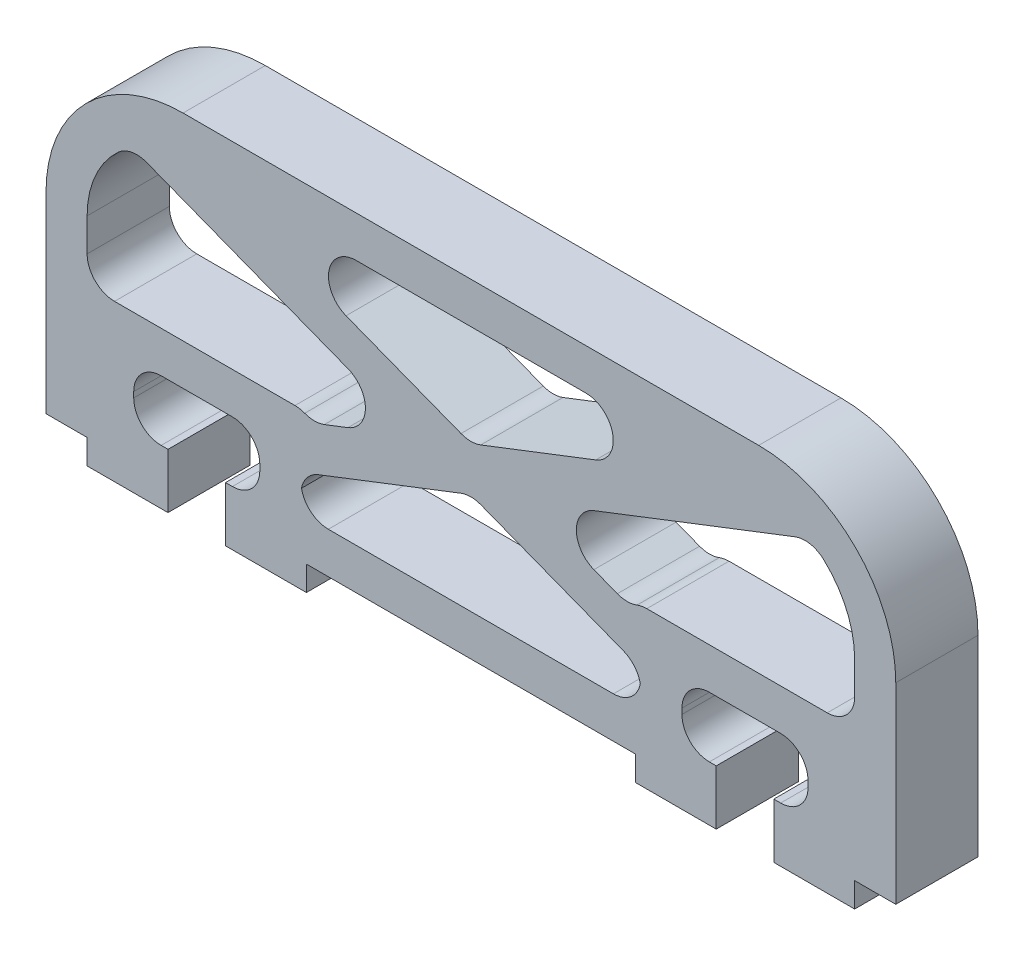
SolidWorks part; units mm, degrees
ref_plane "Front Plane" through (0, 0, 0) normal (0, 0, 1) x (1, 0, 0)
ref_plane "Top Plane" through (0, 0, 0) normal (0, 1, 0) x (1, 0, 0)
ref_plane "Right Plane" through (0, 0, 0) normal (1, 0, 0) x (0, 0, -1)
sketch "Sketch1" plane through (0, 0, 0) normal (0, 0, 1) x (1, 0, 0)
  line L0 (-10, -6.9) -> (-10, 6) construction
  line L1 (-15.5, 6) -> (15.5, 6)
  line L2 (-15.5, 6) -> (-15.5, -6)
  line L3 (-15.5, -6) -> (15.5, -6)
  line L4 (15.5, 6) -> (15.5, -6)
  line L5 (-15.5, 6) -> (15.5, -6) construction
  line L6 (-15.5, -6) -> (15.5, 6) construction
  line L7 (-15.5, -6) -> (-6, -6)
  line L9 (-14, -6.9) -> (-6, -6.9)
  line L10 (-6, -6) -> (-6, -6.9)
  line L11 (0, 6) -> (0, -6) construction
  line L12 (-11.05, -4.9) -> (-8.95, -4.9)
  line L13 (-11.05, -4.9) -> (-11.05, -6.9)
  line L14 (-11.05, -6.9) -> (-8.95, -6.9)
  line L15 (-8.95, -4.9) -> (-8.95, -6.9)
  line L16 (-11.05, -4.9) -> (-8.95, -6.9) construction
  line L17 (-11.05, -6.9) -> (-8.95, -4.9) construction
  line L18 (-12.3, -2.7) -> (-7.7, -2.7)
  line L19 (-12.3, -2.7) -> (-12.3, -4.9)
  line L20 (-12.3, -4.9) -> (-7.7, -4.9)
  line L21 (-7.7, -2.7) -> (-7.7, -4.9)
  line L22 (-12.3, -2.7) -> (-7.7, -4.9) construction
  line L23 (-12.3, -4.9) -> (-7.7, -2.7) construction
  line L24 (12.3, -2.7) -> (7.7, -2.7)
  line L25 (12.3, -2.7) -> (12.3, -4.9)
  line L26 (12.3, -4.9) -> (7.7, -4.9)
  line L27 (7.7, -2.7) -> (7.7, -4.9)
  line L28 (11.05, -4.9) -> (8.95, -4.9)
  line L29 (11.05, -4.9) -> (11.05, -6.9)
  line L30 (11.05, -6.9) -> (8.95, -6.9)
  line L31 (8.95, -4.9) -> (8.95, -6.9)
  line L32 (15.5, -6) -> (6, -6)
  line L33 (6, -6) -> (6, -6.9)
  line L34 (14, -6.9) -> (6, -6.9)
  line L36 (-14, -6.9) -> (-14, -6)
  line L37 (14, -6.9) -> (14, -6)
  line L38 (10, -2.7) -> (10, -6.9) construction
  point P0 (0, 0)
  point P11 (-10, -5.9)
  point P16 (-10, -3.8)
  dimension "D1" = 31
  dimension "D2" = 12
  dimension "D3" = 0.9
  dimension "D4" = 8
  dimension "D5" = 2.1
  dimension "D6" = 2
  dimension "D7" = 2.2
  dimension "D8" = 4.6
  dimension "D9" = 20
extrude "Base shape" add sketch "Sketch1" along normal blind 3 contours L31 L26 L27 L24 L25 L29 L3 L4 L1 L2 L13 L20 L19 L18 L21 L15 | L3 L15 L9 L10 | L13 L3 L9 | L34 L31 L3 L33 | L3 L29 L34 region at (0, 0.2941, 0) region at (-12.525, -6.45, 0) region at (12.525, -6.45, 0) region at (-7.475, -6.45, 0) region at (7.475, -6.45, 0)
fillet "Edge radiuses" radius 5 2 edges at (15.5, 6, 1.5) (-15.5, 6, 1.5)
sketch "Sketch2" plane through (0, 0, 3) normal (0, 0, 1) x (1, 0, 0)
  line L0 (-6, -6) -> (6, -6) construction
  line L1 (15.5, -6) -> (-15.5, -6)
  line L2 (15.5, -6) -> (15.5, 6)
  line L3 (15.5, 6) -> (-15.5, 6)
  line L4 (-15.5, -6) -> (-15.5, 6)
  line L5 (15.5, -6) -> (-15.5, 6) construction
  line L6 (15.5, 6) -> (-15.5, -6) construction
  line L8 (15.7707, -5.3006) -> (-15.2293, 6.6994)
  line L9 (15.2293, 6.6994) -> (-15.7707, -5.3006)
  line L10 (15.2293, -6.6994) -> (-15.7707, 5.3006)
  line L11 (15.7707, 5.3006) -> (-15.2293, -6.6994)
  line L36 (-15.5, 1) -> (-15.5, -6) construction
  line L37 (-13.8, -1.2) -> (-14, -1.2)
  line L38 (13.8, -1.2) -> (14, -1.2)
  line L60 (10.5, 4.5) -> (-10.5, 4.5)
  line L61 (14, -4.5) -> (14, 1)
  line L62 (-13.8, -1.2) -> (-6.2, -1.2)
  line L63 (-6.2, -1.2) -> (-6.2, -4.5)
  line L64 (-6.2, -4.5) -> (6.2, -4.5)
  line L65 (6.2, -4.5) -> (6.2, -1.2)
  line L66 (6.2, -1.2) -> (13.8, -1.2)
  line L67 (14, -4.5) -> (14, 1)
  line L68 (10.5, 4.5) -> (-10.5, 4.5)
  line L70 (-13.8, -1.2) -> (-6.2, -1.2)
  line L71 (-6.2, -1.2) -> (-6.2, -4.5)
  line L72 (-6.2, -4.5) -> (6.2, -4.5)
  line L73 (6.2, -4.5) -> (6.2, -1.2)
  line L74 (6.2, -1.2) -> (13.8, -1.2)
  line L80 (-14, 1) -> (-14, -4.5)
  line L81 (-14, 1) -> (-14, -4.5)
  line L83 (-13.8, -4.5) -> (-13.8, -1.2)
  line L84 (-13.8, -4.5) -> (-13.8, -1.2)
  line L85 (13.8, -1.2) -> (13.8, -4.5)
  line L86 (13.8, -1.2) -> (13.8, -4.5)
  line L87 (13.8, -4.5) -> (14, -4.5)
  line L88 (13.8, -4.5) -> (14, -4.5)
  line L89 (-14, -4.5) -> (-13.8, -4.5)
  line L90 (-14, -4.5) -> (-13.8, -4.5)
  arc A4 (14, 1) -> (10.5, 4.5) centre (10.5, 1) ccw
  arc A5 (14, 1) -> (10.5, 4.5) centre (10.5, 1) ccw
  arc A8 (-10.5, 4.5) -> (-14, 1) centre (-10.5, 1) ccw
  arc A9 (-10.5, 4.5) -> (-14, 1) centre (-10.5, 1) ccw
  point P0 (0, 0)
  dimension "D1" = 1.5
  dimension "D3" = 1.5
extrude "Inner cuts" cut sketch "Sketch2" against normal up to next contours L10 A9 L81 L90 L9 L84 L70 | L9 L68 L8 | L67 A5 L11 L8 L74 L86 L88 | L72 L73 L10 L11 L71 region at (0, -3.156, 3) region at (9.4158, 0.7335, 3) region at (-9.4158, 0.7335, 3) region at (0, 3.2681, 3)
fillet "1mm milling radiuses" radius 1 24 edges at (6.2, -4.5, 1.5) (6.2, -3.2042, 1.5) (-6.2, -4.5, 1.5) (-6.2, -3.2042, 1.5) (0, -0.8042, 1.5) (2.0776, 0, 1.5) (9.5474, 4.5, 1.5) (-9.5474, 4.5, 1.5) (0, 0.8042, 1.5) (-2.0776, 0, 1.5) (14, -1.2, 1.5) (12.3447, 3.9744, 1.5) (-12.3447, 3.9744, 1.5) (-14, -1.2, 1.5) (-7.7, -2.7, 1.5) (-7.7, -4.9, 1.5) (12.3, -4.9, 1.5) (12.3, -2.7, 1.5) (7.7, -2.7, 1.5) (7.7, -4.9, 1.5) (-12.3, -4.9, 1.5) (-12.3, -2.7, 1.5) (6.2, -1.5958, 1.5) (-6.2, -1.5958, 1.5)
fillet "1mm radiuses second pass" radius 1 2 edges at (6.2, -1.2, 1.5) (-6.2, -1.2, 1.5)
